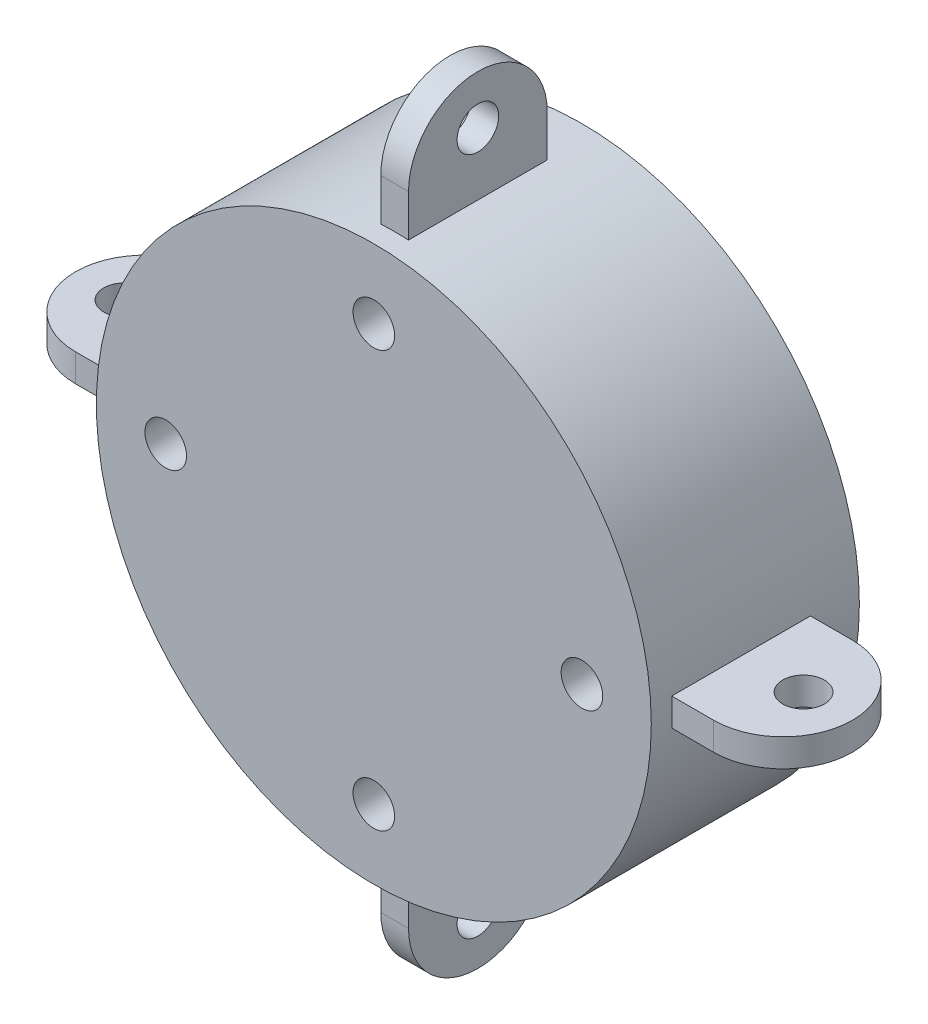
SolidWorks part; units mm, degrees
material "ABS"
ref_plane "前视基准面" through (0, 0, 0) normal (0, 0, 1) x (1, 0, 0)
ref_plane "上视基准面" through (0, 0, 0) normal (0, 1, 0) x (1, 0, 0)
ref_plane "右视基准面" through (0, 0, 0) normal (1, 0, 0) x (0, 0, -1)
sketch "草图1" plane through (0, 0, 0) normal (0, 0, 1) x (1, 0, 0)
  circle A0 centre (0, 0) radius 40
  dimension "D1" = 80
extrude "凸台-拉伸1" add sketch "草图1" along normal blind 30
sketch "草图2" plane through (0, 0, 30) normal (0, 0, 1) x (1, 0, 0)
  line L0 (0, 30) -> (0, 0) construction
  line L1 (0, 0) -> (0, -30) construction
  line L2 (-30, 0) -> (0, 0) construction
  line L3 (0, 0) -> (30, 0) construction
  circle A0 centre (30, 0) radius 3
  circle A1 centre (0, 30) radius 3
  circle A2 centre (-30, 0) radius 3
  circle A3 centre (0, -30) radius 3
  dimension "D1" = 6
  dimension "D2" = 6
  dimension "D7" = 6
  dimension "D8" = 6
  dimension "D3" = 30
  dimension "D4" = 30
  dimension "D5" = 30
  dimension "D6" = 30
extrude "切除-拉伸1" cut sketch "草图2" against normal through all
sketch "草图3" plane through (0, 0, 0) normal (1, 0, 0) x (0, 0, -1)
  line L0 (-7, 38) -> (-27, 38)
  line L1 (-27, 38) -> (-27, 46)
  line L2 (-7, 46) -> (-7, 38)
  line L3 (0, 0) -> (-35.6052, 0) construction
  arc A0 (-27, 46) -> (-7, 46) centre (-17, 46) cw
  dimension "D3" = 10
  dimension "D1" = 38
  dimension "D2" = 8
  dimension "D4" = 7
extrude "凸台-拉伸2" add sketch "草图3" along normal blind 2 and the other way blind 2
sketch "草图4" plane through (2, 0, 0) normal (1, 0, 0) x (0, 0, -1)
  line L0 (-27, 39.95) -> (-7, 39.95) construction
  line L1 (-7, 39.95) -> (-7, 46) construction
  circle A0 centre (-17, 48.95) radius 3
  dimension "D1" = 6
  dimension "D2" = 9
  dimension "D3" = 10
extrude "切除-拉伸2" cut sketch "草图4" against normal through all
pattern_circular "阵列(圆周)2" count 4 every 90 about axis through (0, 0, 30) along (0, 0, -1) of "凸台-拉伸2", "切除-拉伸2"
